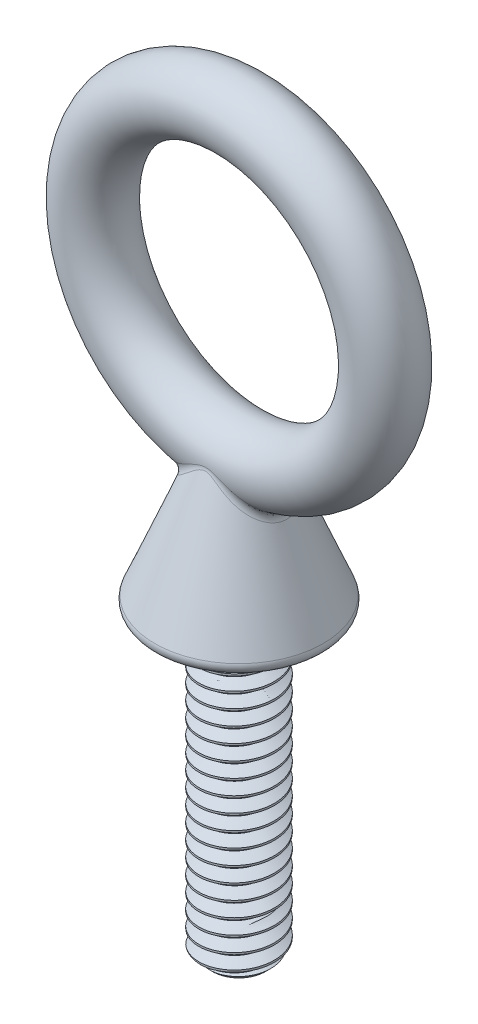
SolidWorks part; units mm, degrees
note: '?' marks a value the reader was unsure of.
ref_plane "Front Plane" through (0, 0, 0) normal (0, 0, 1) x (1, 0, 0)
ref_plane "Top Plane" through (0, 0, 0) normal (0, 1, 0) x (1, 0, 0)
ref_plane "Right Plane" through (0, 0, 0) normal (1, 0, 0) x (0, 0, -1)
sketch "Sketch1" plane through (0, 0, 0) normal (0, 0, 1) x (1, 0, 0)
  line L0 (0, -15.0812) -> (0, -49.2125) construction
  line L1 (-3.175, -49.2125) -> (3.175, -49.2125) construction
  line L2 (3.3125, -49.1331) -> (3.3125, -50.4031) construction
  line L3 (0, -15.0812) -> (0, -9.525) construction
  line L4 (-7.1437, -23.8125) -> (7.1438, -23.8125) construction
  line L5 (3.3125, -50.4031) -> (2.2126, -49.7681) construction
  line L6 (2.2126, -49.7681) -> (3.3125, -49.1331) construction
  line L7 (2.2126, -49.7681) -> (2.3501, -49.7681) construction
  line L8 (3.3125, -49.7681) -> (3.175, -49.7681) construction
  line L9 (2.3501, -49.8475) -> (2.3501, -49.6887) construction
  line L10 (3.175, -50.3238) -> (3.175, -49.2125) construction
  line L11 (3.2437, -50.3634) -> (3.2437, -49.1728) construction
  circle A0 centre (0, 0) radius 15.0813 construction
  circle A1 centre (0, 12.3031) radius 2.7781 construction
  circle A2 centre (0, 0) radius 9.525 construction
  point P7 (0, -15.0812)
  point P9 (0, -23.8125)
  point P10 (0, 15.0812)
  point P11 (0, 9.525)
  point P14 (0, -49.2125)
  point P17 (0, 0)
  point P19 (0, -12.3031)
  point P21 (0, -23.8125)
  point P32 (2.3501, -49.7681)
  point P35 (3.175, -49.7681)
  point P38 (3.2437, -49.7681)
  dimension "Pitch" = 1.27
  dimension "D1" = 0.1588
sketch "Sketch2" plane through (0, 0, 0) normal (0, 1, 0) x (1, 0, 0)
  circle A0 centre (0, 0) radius 3.175
extrude "Boss-Extrude1" add sketch "Sketch2" against normal up to vertex (49.2125 mm away) from vertex at -23.8125 starting at point (0, -23.8125, 0)
sketch "Sketch3" plane through (0, -49.2125, 0) normal (0, -1, 0) x (1, 0, 0)
  circle A1 centre (0, 0) radius 2.2126
  circle A2 centre (0, 0) radius 2.2126
  point P0 (3.175, 0)
  point P1 (0, -3.175)
  dimension "D1" = 0
sketch "Sketch4" plane through (0, 0, 0) normal (0, 0, 1) x (1, 0, 0)
  line L0 (2.3501, -49.6887) -> (2.3501, -49.8475)
  line L1 (2.3501, -49.8475) -> (3.2437, -50.3634)
  line L2 (3.2437, -50.3634) -> (3.2437, -49.1728)
  line L3 (3.2437, -49.1728) -> (2.3501, -49.6887)
sketch "Sketch5" plane through (0, -49.2125, 0) normal (0, -1, 0) x (1, 0, 0)
  circle A0 centre (0, 0) radius 2.2126
extrude "Cut-Extrude1" cut sketch "Sketch5" against normal through all draft 45 flip side to cut
sketch "Sketch6" plane through (0, 0, 0) normal (1, 0, 0) x (0, 0, -1)
  circle A0 centre (0, 12.3031) radius 2.7781
ref_axis "Axis1" through (0, 0, -7.6398) along (0, 0, 1)
revolve "Revolve1" add sketch "Sketch6" angle 360 about axis through (0, 0, -7.6398) along (0, 0, 1)
sketch "Sketch8" plane through (0, 0, 0) normal (0, 0, 1) x (1, 0, 0)
  line L0 (0, -23.8125) -> (0, -12.3031)
  line L1 (0, -12.3031) -> (-2.7781, -12.3031)
  line L2 (-6.4492, -23.8125) -> (-7.1437, -23.8125) construction
  line L3 (-7.1437, -23.8125) -> (-7.1437, -23.118) construction
  line L4 (0, -23.8125) -> (7.1437, -23.8125) construction
  line L5 (-7.1437, -23.8125) -> (7.1438, -23.8125) construction
  line L6 (-7.0921, -22.8551) -> (-2.7781, -12.3031)
  line L7 (-7.1437, -23.8125) -> (0, -23.8125) construction
  line L9 (-6.4492, -23.8125) -> (0, -23.8125)
  arc A0 (-7.0921, -22.8551) -> (-6.4492, -23.8125) centre (-6.4492, -23.118) ccw
  circle A1 centre (0, -12.3031) radius 2.7781 construction
  dimension "D1" = 0.6945
revolve "Revolve2" add sketch "Sketch8" angle 360 about L0
fillet "Fillet1" radius 0.6945 1 edges at (3.2544, -14.2744, 1.5013)
sketch "SketchX" plane through (0, 0, 0) normal (1, 0, 0) x (0, 0, -1)
  line L0 (3.175, -49.2125) -> (3.175, -46.0375) construction
  line L1 (0, -49.2125) -> (3.175, -49.2125) construction
  dimension "D1" = 3.175
  dimension "D2" = 3.175
ref_axis "Center Axis 1" through (0, 21.5506, 0) along (0, -1, 0)?
ref_axis "Center Axis 2" through (0, 0, -7.6398) along (0, 0, 1)?
curve "Helix/Spiral1" pitch 1.27 height 26.67 turns 21 parameters "Pitch"=1.27
ref_plane "Plane1" through (0, -23.8125, 0) normal (0, -1, 0) x (1, 0, 0)
split "Split1" trim tools "Plane1" bodies to split 109 resulting bodies 110 111
sweep "Cut-Sweep1" cut profiles "Sketch4" path "Helix/Spiral1" align with end faces yes
sketch "Sketch9" plane through (0, -23.8125, 0) normal (0, -1, 0) x (1, 0, 0)
  line L0 (-7.1437, 0) -> (7.1438, 0) construction
  circle A0 centre (0, 0) radius 3.175
extrude "Boss-Extrude2" add sketch "Sketch9" along normal blind 2.54 draft 45
equation "\"D3@Helix/Spiral1\" = \"Pitch@Helix/Spiral1\" + \"Thread Lg.@Sketch1\""
equation "\"D1@Sketch8\" = \"A@Sketch1\" / 8"
equation "\"D1@Fillet1\" = \"A@Sketch1\" / 8"
equation "\"D1@SketchX\"= \"Pitch@Helix/Spiral1\"*2.5"
equation "\"D1@Sketch1\"=\"Pitch@Sketch1\"/8"
equation "\"Pitch@Helix/Spiral1\"=\"Pitch@Sketch1\""
equation "\"D2@SketchX\" = \"Thread OD@Sketch1\" / 2"
